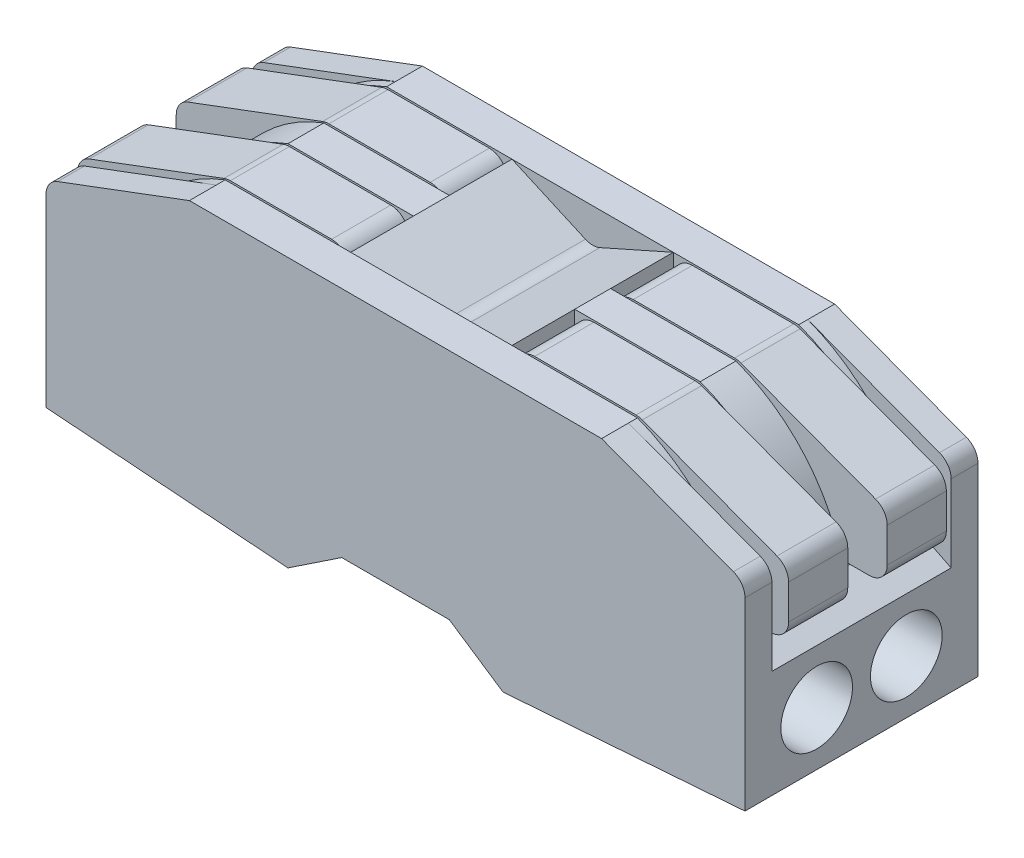
SolidWorks part; units mm, degrees
ref_plane "Alzado" through (0, 0, 0) normal (0, 0, 1) x (1, 0, 0)
ref_plane "Planta" through (0, 0, 0) normal (0, 1, 0) x (1, 0, 0)
ref_plane "Vista lateral" through (0, 0, 0) normal (1, 0, 0) x (0, 0, -1)
sketch "Croquis1" plane through (0, 0, 0) normal (0, 0, 1) x (1, 0, 0)
  line L0 (0, 7.5) -> (0, -7.5) construction
  line L1 (-19.5, 7.5) -> (19.5, 7.5)
  line L2 (-19.5, 7.5) -> (-19.5, -7.5)
  line L3 (-19.5, -7.5) -> (19.5, -7.5)
  line L4 (19.5, 7.5) -> (19.5, -7.5)
  line L5 (-19.5, 7.5) -> (19.5, -7.5) construction
  line L6 (-19.5, -7.5) -> (19.5, 7.5) construction
  point P0 (0, 0)
  dimension "D1" = 39
  dimension "D2" = 15
extrude "Saliente-Extruir1" add sketch "Croquis1" along normal blind 13
sketch "Croquis2" plane through (0, 0, 13) normal (0, 0, 1) x (1, 0, 0)
  line L0 (-19.5, -7.5) -> (19.5, -7.5) construction
  line L1 (0, -7.5) -> (0, 7.5) construction
  line L2 (19.5, 7.5) -> (-19.5, 7.5) construction
  line L3 (-6, -7.5) -> (-19.5, -6.5)
  line L4 (-19.5, 7.5) -> (-19.5, -7.5) construction
  line L5 (-19.5, -6.5) -> (-19.5, -7.5)
  line L6 (-19.5, -7.5) -> (-6, -7.5)
  line L7 (-3, -5.5) -> (-6, -7.5)
  line L8 (-3, -5.5) -> (3, -5.5)
  line L9 (6, -7.5) -> (-6, -7.5)
  line L10 (3, -5.5) -> (6, -7.5)
  line L11 (19.5, -7.5) -> (6, -7.5)
  line L12 (19.5, -6.5) -> (19.5, -7.5)
  line L13 (6, -7.5) -> (19.5, -6.5)
  point P0 (-6, -7.5)
  point P8 (-3, -5.5)
  point P17 (0, -5.5)
  dimension "D1" = 6
  dimension "D2" = 1
  dimension "D3" = 3
  dimension "D4" = 2
extrude "Cortar-Extruir1" cut sketch "Croquis2" against normal blind 13 contours L1 L9 L10 L8 | L1 L8 L7 | L3 | L13 L12 L11 region at (-2.3333, -6.6111, 13) region at (2.3333, -6.6111, 13) region at (-15, -7.1667, 13)
sketch "Croquis3" plane through (0, 0, 13) normal (0, 0, 1) x (1, 0, 0)
  line L0 (19.5, 7.5) -> (-19.5, 7.5) construction
  line L1 (0, 7.5) -> (0, 0) construction
  line L2 (-19.5, 7.5) -> (-19.5, -6.5) construction
  line L3 (-11.5, 7.5) -> (-19.5, 4.5)
  line L4 (-19.5, 4.5) -> (-19.5, 7.5)
  line L5 (-19.5, 7.5) -> (-11.5, 7.5)
  line L6 (19.5, 4.5) -> (19.5, 7.5)
  line L7 (11.5, 7.5) -> (19.5, 4.5)
  line L8 (19.5, 7.5) -> (11.5, 7.5)
  point P0 (-11.5, 7.5)
  point P6 (-19.5, 4.5)
  point P7 (-19.5, -6.5)
  dimension "D1" = 11.5
  dimension "D2" = 11
extrude "Cortar-Extruir2" cut sketch "Croquis3" against normal through all
sketch "Croquis4" plane through (19.5, 0, 0) normal (1, 0, 0) x (0, 0, -1)
  line L0 (0, -6.5) -> (-13, -6.5) construction
  line L2 (-11, -6.5) -> (-11, -7.5)
  line L3 (-11, -7.5) -> (-2, -7.5)
  line L4 (-2, -6.5) -> (-2, -7.5)
  line L5 (-6.5, -6.5) -> (-2, -7.5) construction
  line L6 (-11, -7.5) -> (-6.5, -6.5) construction
  line L7 (0, -7.5) -> (-13, -7.5) construction
  line L8 (0, -6.5) -> (0, 4.5) construction
  line L9 (-2, -6.5) -> (-11, -6.5)
  line L10 (-13, -7.5) -> (-13, -6.5) construction
  point P0 (-6.5, -6.5)
  dimension "D1" = 2
  dimension "D2" = 2
extrude "Cortar-Extruir3" cut sketch "Croquis4" against normal blind 10
sketch "Croquis5" plane through (-19.5, 0, 0) normal (-1, 0, 0) x (0, 0, 1)
  line L0 (0, -6.5) -> (13, -6.5) construction
  line L2 (2, -6.5) -> (2, -7.5)
  line L3 (2, -7.5) -> (11, -7.5)
  line L4 (11, -6.5) -> (11, -7.5)
  line L5 (6.5, -6.5) -> (11, -7.5) construction
  line L6 (2, -7.5) -> (6.5, -6.5) construction
  line L7 (0, -7.5) -> (13, -7.5) construction
  line L8 (13, -7.5) -> (13, -6.5) construction
  line L9 (11, -6.5) -> (2, -6.5)
  point P0 (6.5, -6.5)
  dimension "D1" = 2
extrude "Cortar-Extruir4" cut sketch "Croquis5" against normal blind 10
sketch "Croquis6" plane through (0, 0, 0) normal (0, 0, -1) x (-1, 0, 0)
  line L0 (0, 7.5) -> (0, 1.4685) construction
  line L1 (-11.5, 7.5) -> (11.5, 7.5) construction
  line L2 (4.5, 7.5) -> (-4.5, 7.5)
  line L3 (-4.5, 7.5) -> (0, 5.5)
  line L4 (4.5, 7.5) -> (0, 5.5)
  point P5 (-4.5, 7.5)
  dimension "D1" = 4.5
  dimension "D2" = 2
extrude "Cortar-Extruir5" cut sketch "Croquis6" against normal offset from surface (9 mm away) 2 from offset 2 up to face at (0, -1.5, 13) offset against normal yes
sketch "Croquis7" plane through (-19.5, 0, 0) normal (-1, 0, 0) x (0, 0, 1)
  line L3 (6.5, -6.5) -> (6.5, 4.5) construction
  line L4 (11, -6.5) -> (2, -6.5) construction
  line L5 (0, 4.5) -> (13, 4.5) construction
  line L6 (13, 4.5) -> (13, -6.5) construction
  line L11 (11, -6.5) -> (2, -6.5) construction
  circle A2 centre (9, -3.5) radius 2
  circle A3 centre (4, -3.5) radius 2
  dimension "D1" = 1
  dimension "D3" = 2
extrude "Cortar-Extruir10" cut sketch "Croquis7" against normal blind 15
sketch "Croquis8" plane through (19.5, 0, 0) normal (1, 0, 0) x (0, 0, -1)
  circle A0 centre (-9, -3.5) radius 2
  circle A1 centre (-4, -3.5) radius 2
extrude "Cortar-Extruir11" cut sketch "Croquis8" against normal blind 15
sketch "Croquis9" plane through (0, 7.5, 0) normal (0, 1, 0) x (1, 0, 0)
  line L0 (-19.5, -6.5) -> (19.5, -6.5) construction
  line L1 (-19.5, 0) -> (-19.5, -13) construction
  line L2 (19.5, 0) -> (19.5, -13) construction
  line L3 (4.5, -5.5) -> (19.5, -5.5)
  line L4 (4.5, -11) -> (4.5, -2) construction
  line L5 (-4.5, -5.5) -> (-19.5, -5.5)
  line L6 (-4.5, -11) -> (-4.5, -2) construction
  line L7 (-4.5, -7.5) -> (-19.5, -7.5)
  line L8 (4.5, -7.5) -> (19.5, -7.5)
  line L9 (4.5, -7.5) -> (4.5, -11)
  line L10 (4.5, -11) -> (19.5, -11)
  line L11 (19.5, -11) -> (19.5, -7.5)
  line L12 (4.5, -5.5) -> (4.5, -2)
  line L13 (4.5, -2) -> (19.5, -2)
  line L14 (19.5, -2) -> (19.5, -5.5)
  line L15 (-4.5, -5.5) -> (-4.5, -2)
  line L16 (-4.5, -2) -> (-19.5, -2)
  line L17 (-19.5, -2) -> (-19.5, -5.5)
  line L18 (-19.5, -7.5) -> (-19.5, -11)
  line L19 (-19.5, -11) -> (-4.5, -11)
  line L20 (-4.5, -11) -> (-4.5, -7.5)
  line L21 (-19.5, -13) -> (-11.5, -13) construction
  line L22 (11.5, 0) -> (19.5, 0) construction
  line L23 (11.5, 0) -> (-11.5, 0) construction
  dimension "D1" = 1
  dimension "D2" = 2
  dimension "D3" = 2
  dimension "D4" = 2
extrude "Cortar-Extruir12" cut sketch "Croquis9" against normal blind 7
sketch "Croquis10" plane through (0, 0, 5.5) normal (0, 0, -1) x (-1, 0, 0)
  line L0 (19.5, 0.5) -> (4.5, 0.5) construction
  line L1 (19.5, 4.5) -> (19.5, -6.5) construction
  line L2 (11.5, 7.5) -> (19.5, 4.5) construction
  line L3 (17.5, 0.5) -> (19.5, 0.5)
  line L4 (19.5, 0.5) -> (19.5, 4.5)
  line L5 (19.5, 4.5) -> (11.5, 7.5)
  line L6 (0, 7.5) -> (0, -5.5) construction
  line L7 (4.5, 7.5) -> (-4.5, 7.5) construction
  line L8 (3, -5.5) -> (-3, -5.5) construction
  line L9 (-19.5, 4.5) -> (-11.5, 7.5)
  line L10 (-19.5, 0.5) -> (-19.5, 4.5)
  line L11 (-17.5, 0.5) -> (-19.5, 0.5)
  arc A0 (11.5, 7.5) -> (17.5, 0.5) centre (8.1447, -1.4474) cw
  arc A1 (-11.5, 7.5) -> (-17.5, 0.5) centre (-8.1447, -1.4474) ccw
  point P0 (17.5, 0.5)
  dimension "D1" = 2
extrude "Cortar-Extruir13" cut sketch "Croquis10" against normal blind 6 and the other way blind 4
chamfer "Chaflán1" distance 1 distance2 2 2 edges at (-19.5, 0.5, 6.5) (19.5, 0.5, 6.5) first distance on face at (-19.5, -5.5, 9) first distance on face at (19.5, -1.5, 4)
sketch "Croquis11" plane through (0, 0, 7.5) normal (0, 0, 1) x (1, 0, 0)
  line L0 (11.5, 7.5) -> (19.8336, 4.3749)
  line L1 (4.6639, 0.7529) -> (19.8336, 0.7529)
  line L2 (4.6639, 0.7529) -> (4.6639, 7.5)
  line L3 (4.6639, 7.5) -> (11.5, 7.5)
  line L6 (19.8336, 0.7529) -> (19.8336, 4.3749)
  line L7 (0, 7.5) -> (0, 0) construction
  line L8 (-4.5, 7.5) -> (4.5, 7.5) construction
  line L9 (-19.8336, 0.7529) -> (-19.8336, 4.3749)
  line L10 (-4.6639, 7.5) -> (-11.5, 7.5)
  line L11 (-4.6639, 0.7529) -> (-4.6639, 7.5)
  line L12 (-4.6639, 0.7529) -> (-19.8336, 0.7529)
  line L13 (-11.5, 7.5) -> (-19.8336, 4.3749)
extrude "Saliente-Extruir2" add sketch "Croquis11" along normal offset from surface (3.3 mm away) 0.1 from offset 0.1 separate body up to face at (-9.725, 4.1929, 11)
sketch "Croquis12" plane through (0, 0, 7.6) normal (0, 0, -1) x (-1, 0, 0)
  line L0 (11.5, 7.5) -> (19.8336, 4.3749)
  line L1 (4.6639, 0.7529) -> (19.8336, 0.7529)
  line L2 (4.6639, 0.7529) -> (4.6639, 7.5)
  line L3 (4.6639, 7.5) -> (11.5, 7.5)
  line L4 (19.8336, 0.7529) -> (19.8336, 4.3749)
  line L5 (0, 7.5) -> (0, 0) construction
  line L6 (-19.8336, 0.7529) -> (-19.8336, 4.3749)
  line L7 (-4.6639, 7.5) -> (-11.5, 7.5)
  line L8 (-4.6639, 0.7529) -> (-4.6639, 7.5)
  line L9 (-4.6639, 0.7529) -> (-19.8336, 0.7529)
  line L10 (-11.5, 7.5) -> (-19.8336, 4.3749)
extrude "Saliente-Extruir3" add sketch "Croquis12" along normal offset from surface (3.3 mm away) 0.1 from offset 2.2 separate body up to face at (9.725, 4.1929, 2)
fillet "Redondeo1" radius 1 1 edges at (4.6639, 7.5, 3.75)
fillet "Redondeo2" radius 1 1 edges at (4.6639, 7.5, 9.25)
fillet "Redondeo3" radius 1 1 edges at (-4.6639, 7.5, 3.75)
fillet "Redondeo4" radius 1 1 edges at (-4.6639, 7.5, 9.25)
fillet "Redondeo5" radius 1 1 edges at (-11.5, 7.5, 9.25)
fillet "Redondeo6" radius 1 1 edges at (-11.5, 7.5, 3.75)
fillet "Redondeo7" radius 1 1 edges at (11.5, 7.5, 9.25)
fillet "Redondeo8" radius 1 1 edges at (11.5, 7.5, 3.75)
fillet "Redondeo12" radius 1 1 edges at (0, 5.5, 6.5)
fillet "Redondeo13" radius 1 4 edges at (-19.5, 4.5, 0.75) (-19.5, 4.5, 12.25) (19.5, 4.5, 12.25) (19.5, 4.5, 0.75)
fillet "Redondeo14" radius 1 2 edges at (-19.8336, 0.7529, 3.75) (-19.8336, 4.3749, 3.75)
fillet "Redondeo15" radius 1 2 edges at (-19.8336, 0.7529, 9.25) (-19.8336, 4.3749, 9.25)
fillet "Redondeo16" radius 1 2 edges at (19.8336, 4.3749, 3.75) (19.8336, 0.7529, 3.75)
fillet "Redondeo17" radius 1 2 edges at (19.8336, 0.7529, 9.25) (19.8336, 4.3749, 9.25)
sketch "Croquis13" [suppressed] plane through (0, 0, 0) normal (0, 0, 1) x (1, 0, 0)
  line L1 (-19.5, 7.5) -> (19.5, 7.5)
  line L2 (-19.5, 7.5) -> (-19.5, -7.5)
  line L3 (-19.5, -7.5) -> (19.5, -7.5)
  line L4 (19.5, 7.5) -> (19.5, -7.5)
  line L5 (-19.5, 7.5) -> (19.5, -7.5) construction
  line L6 (-19.5, -7.5) -> (19.5, 7.5) construction
  point P0 (0, 0)
  dimension "D1" = 39
  dimension "D2" = 15
extrude "Saliente-Extruir4" [suppressed] add sketch "Croquis13" along normal blind 18
sketch "Croquis14" [suppressed] plane through (0, 0, 18) normal (0, 0, 1) x (1, 0, 0)
  line L0 (-19.5, -7.5) -> (19.5, -7.5) construction
  line L1 (0, -7.5) -> (0, 7.5) construction
  line L3 (-6, -7.5) -> (-19.5, -6.5)
  line L5 (-19.5, -6.5) -> (-19.5, -7.5)
  line L6 (-19.5, -7.5) -> (-6, -7.5)
  line L7 (-3, -5.5) -> (-6, -7.5)
  line L8 (-3, -5.5) -> (3, -5.5)
  line L9 (6, -7.5) -> (-6, -7.5)
  line L10 (3, -5.5) -> (6, -7.5)
  line L11 (19.5, -7.5) -> (6, -7.5)
  line L12 (19.5, -6.5) -> (19.5, -7.5)
  line L13 (6, -7.5) -> (19.5, -6.5)
  point P0 (-6, -7.5)
  point P2 (0, -7.5)
  point P8 (-3, -5.5)
  point P17 (0, -5.5)
  dimension "D1" = 6
  dimension "D3" = 3
extrude "Cortar-Extruir15" [suppressed] cut sketch "Croquis14" against normal blind 18
sketch "Croquis15" [suppressed] plane through (0, 0, 0) normal (0, 0, 1) x (1, 0, 0)
  line L1 (0, 7.5) -> (0, 0) construction
  line L3 (-11.5, 7.5) -> (-19.5, 4.5)
  line L4 (-19.5, 4.5) -> (-19.5, 7.5)
  line L5 (-19.5, 7.5) -> (-11.5, 7.5)
  line L6 (19.5, 4.5) -> (19.5, 7.5)
  line L7 (11.5, 7.5) -> (19.5, 4.5)
  line L8 (19.5, 7.5) -> (11.5, 7.5)
  point P0 (-11.5, 7.5)
  point P6 (-19.5, 4.5)
  dimension "D1" = 11.5
extrude "Cortar-Extruir17" [suppressed] cut sketch "Croquis15" along normal through all
sketch "Croquis16" [suppressed] plane through (19.5, 0, 0) normal (1, 0, 0) x (0, 0, -1)
  line L0 (0, -6.5) -> (-18, -6.5) construction
  line L2 (-16, -6.5) -> (-16, -7.5)
  line L3 (-16, -7.5) -> (-2, -7.5)
  line L4 (-2, -6.5) -> (-2, -7.5)
  line L5 (-9, -6.5) -> (-2, -7.5) construction
  line L6 (-16, -7.5) -> (-9, -6.5) construction
  line L7 (0, -6.5) -> (0, 4.5) construction
  line L9 (0, -7.5) -> (-18, -7.5) construction
  line L10 (-16, -6.5) -> (-2, -6.5)
  point P0 (-9, -6.5)
  dimension "D1" = 2
  dimension "D2" = 0
extrude "Cortar-Extruir18" [suppressed] cut sketch "Croquis16" against normal blind 10
sketch "Croquis17" [suppressed] plane through (-19.5, 0, 0) normal (-1, 0, 0) x (0, 0, 1)
  line L0 (0, -6.5) -> (18, -6.5) construction
  line L2 (2, -6.5) -> (2, -7.5)
  line L3 (2, -7.5) -> (16, -7.5)
  line L4 (16, -6.5) -> (16, -7.5)
  line L5 (9, -6.5) -> (16, -7.5) construction
  line L6 (2, -7.5) -> (9, -6.5) construction
  line L7 (0, -7.5) -> (18, -7.5) construction
  line L8 (18, 4.5) -> (18, -6.5) construction
  line L9 (2, -6.5) -> (16, -6.5)
  point P0 (9, -6.5)
  dimension "D1" = 2
extrude "Cortar-Extruir19" [suppressed] cut sketch "Croquis17" against normal blind 10
sketch "Croquis18" [suppressed] plane through (0, 0, 18) normal (0, 0, 1) x (1, 0, 0)
  line L0 (0, 7.5) -> (0, 1.4685) construction
  line L2 (4.5, 7.5) -> (-4.5, 7.5)
  line L3 (-4.5, 7.5) -> (0, 5.5)
  line L4 (4.5, 7.5) -> (0, 5.5)
  line L5 (11.5, 7.5) -> (-11.5, 7.5) construction
  point P2 (0, 7.5)
  point P5 (-4.5, 7.5)
  dimension "D1" = 4.5
  dimension "D2" = 2
extrude "Cortar-Extruir20" [suppressed] cut sketch "Croquis18" against normal offset from surface (14 mm away) 2 from offset 2 offset against normal yes
sketch "Croquis19" [suppressed] plane through (0, 7.5, 0) normal (0, 1, 0) x (1, 0, 0)
  line L0 (-19.5, -9) -> (19.5, -9) construction
  line L1 (-19.5, -18) -> (-19.5, 0) construction
  line L2 (19.5, -18) -> (19.5, 0) construction
  line L3 (4.5, -7.5) -> (19.5, -7.5)
  line L4 (4.5, -2) -> (4.5, -16) construction
  line L5 (-4.5, -7.5) -> (-19.5, -7.5)
  line L6 (-4.5, -2) -> (-4.5, -16) construction
  line L7 (-19.5, -7.5) -> (-19.5, -10.5)
  line L8 (-19.5, -10.5) -> (-4.5, -10.5)
  line L9 (-4.5, -7.5) -> (-4.5, -10.5)
  line L10 (4.5, -10.5) -> (19.5, -10.5)
  line L11 (19.5, -10.5) -> (19.5, -7.5)
  line L12 (4.5, -7.5) -> (4.5, -10.5)
  line L13 (-19.5, -9) -> (-19.5, 0) construction
  line L14 (-19.5, -9) -> (-19.5, -18) construction
  line L15 (4.5, -15.375) -> (19.5, -15.375)
  line L16 (-19.5, -13.875) -> (19.5, -13.875) construction
  line L25 (4.5, -15.375) -> (19.5, -15.375)
  line L26 (-19.5, -12.375) -> (-19.5, -15.375)
  line L27 (-4.5, -12.375) -> (-4.5, -15.375)
  line L28 (-4.5, -12.375) -> (-19.5, -12.375)
  line L29 (-19.5, -15.375) -> (-4.5, -15.375)
  line L30 (19.5, -15.375) -> (19.5, -12.375)
  line L31 (4.5, -12.375) -> (4.5, -15.375)
  line L32 (4.5, -12.375) -> (19.5, -12.375)
  line L33 (0, 0) -> (0, -18) construction
  line L34 (11.5, -18) -> (-11.5, -18) construction
  line L35 (-19.5, -12.375) -> (-4.5, -12.375)
  line L36 (-4.5, -15.375) -> (-19.5, -15.375)
  line L37 (4.5, -12.375) -> (19.5, -12.375)
  line L38 (-19.5, -4.125) -> (19.5, -4.125) construction
  line L39 (4.5, -5.625) -> (19.5, -5.625)
  line L40 (-4.5, -2.625) -> (-19.5, -2.625)
  line L41 (-19.5, -5.625) -> (-4.5, -5.625)
  line L42 (4.5, -5.625) -> (19.5, -5.625)
  line L43 (4.5, -5.625) -> (4.5, -2.625)
  line L44 (19.5, -2.625) -> (19.5, -5.625)
  line L45 (-19.5, -2.625) -> (-4.5, -2.625)
  line L46 (-4.5, -5.625) -> (-19.5, -5.625)
  line L47 (-4.5, -5.625) -> (-4.5, -2.625)
  line L48 (-19.5, -5.625) -> (-19.5, -2.625)
  line L49 (4.5, -2.625) -> (19.5, -2.625)
  line L50 (4.5, -2.625) -> (19.5, -2.625)
  dimension "D1" = 3
  dimension "D2" = 1.5
  dimension "D3" = 3
extrude "Cortar-Extruir21" [suppressed] cut sketch "Croquis19" against normal blind 7
sketch "Croquis23" [suppressed] plane through (0, 0, 7.5) normal (0, 0, 1) x (1, 0, 0)
  line L0 (11.5, 7.5) -> (19.8336, 4.3749)
  line L1 (4.6639, 0.7529) -> (19.8336, 0.7529)
  line L2 (4.6639, 0.7529) -> (4.6639, 7.5)
  line L3 (4.6639, 7.5) -> (11.5, 7.5)
  line L4 (19.8336, 0.7529) -> (19.8336, 4.3749)
  line L5 (0, 7.5) -> (0, 0) construction
  line L6 (-19.8336, 0.7529) -> (-19.8336, 4.3749)
  line L7 (-4.6639, 7.5) -> (-11.5, 7.5)
  line L8 (-4.6639, 0.7529) -> (-4.6639, 7.5)
  line L9 (-4.6639, 0.7529) -> (-19.8336, 0.7529)
  line L10 (-11.5, 7.5) -> (-19.8336, 4.3749)
  line L11 (-4.5, 7.5) -> (4.5, 7.5) construction
  point P4 (0, 7.5)
extrude "Saliente-Extruir6" [suppressed] add sketch "Croquis23" along normal offset from surface (2.8 mm away) 0.1 from offset 0.1 separate body
sketch "Croquis25" [suppressed] plane through (0, 0, 12.375) normal (0, 0, 1) x (1, 0, 0)
  line L0 (11.5, 7.5) -> (19.8336, 4.3749)
  line L1 (4.6639, 0.7529) -> (19.8336, 0.7529)
  line L2 (4.6639, 0.7529) -> (4.6639, 7.5)
  line L3 (4.6639, 7.5) -> (11.5, 7.5)
  line L4 (19.8336, 0.7529) -> (19.8336, 4.3749)
  line L5 (0, 7.5) -> (0, 0) construction
  line L6 (-19.8336, 0.7529) -> (-19.8336, 4.3749)
  line L7 (-4.6639, 7.5) -> (-11.5, 7.5)
  line L8 (-4.6639, 0.7529) -> (-4.6639, 7.5)
  line L9 (-4.6639, 0.7529) -> (-19.8336, 0.7529)
  line L10 (-11.5, 7.5) -> (-19.8336, 4.3749)
  line L11 (-4.5, 7.5) -> (4.5, 7.5) construction
  point P16 (0, 7.5)
extrude "Saliente-Extruir7" [suppressed] add sketch "Croquis25" along normal offset from surface (2.8 mm away) 0.1 from offset 0.1 separate body
sketch "Croquis27" [suppressed] plane through (0, 0, 2.625) normal (0, 0, 1) x (1, 0, 0)
  line L0 (11.5, 7.5) -> (19.8336, 4.3749)
  line L1 (4.6639, 0.7529) -> (19.8336, 0.7529)
  line L2 (4.6639, 0.7529) -> (4.6639, 7.5)
  line L3 (4.6639, 7.5) -> (11.5, 7.5)
  line L4 (19.8336, 0.7529) -> (19.8336, 4.3749)
  line L5 (0, 7.5) -> (0, 0) construction
  line L6 (-19.8336, 0.7529) -> (-19.8336, 4.3749)
  line L7 (-4.6639, 7.5) -> (-11.5, 7.5)
  line L8 (-4.6639, 0.7529) -> (-4.6639, 7.5)
  line L9 (-4.6639, 0.7529) -> (-19.8336, 0.7529)
  line L10 (-11.5, 7.5) -> (-19.8336, 4.3749)
  line L12 (-4.5, 7.5) -> (4.5, 7.5) construction
  point P4 (0, 7.5)
  point P16 (0, 7.5)
extrude "Saliente-Extruir8" [suppressed] add sketch "Croquis27" along normal offset from surface (2.8 mm away) 0.1 from offset 0.1 separate body
fillet "Redondeo19" [suppressed] radius 1
fillet "Redondeo20" [suppressed] radius 1
fillet "Redondeo21" [suppressed] radius 1
fillet "Redondeo22" [suppressed] radius 1
fillet "Redondeo24" [suppressed] radius 1
sketch "Croquis26" [suppressed] plane through (-19.5, 0, 0) normal (-1, 0, 0) x (0, 0, 1)
  line L0 (4.125, 0.5) -> (4.125, -6.5) construction
  line L2 (16, -6.5) -> (2, -6.5) construction
  line L3 (9, 0.5) -> (9, -6.5) construction
  line L5 (16, -6.5) -> (2, -6.5) construction
  line L6 (13.875, 0.5) -> (13.875, -6.5) construction
  line L9 (13.875, -3.5) -> (4.125, -3.5) construction
  line L13 (15.375, 0.5) -> (12.375, 0.5) construction
  line L14 (10.5, 0.5) -> (7.5, 0.5) construction
  line L15 (5.625, 0.5) -> (2.625, 0.5) construction
  circle A0 centre (13.875, -3.5) radius 2
  circle A1 centre (9, -3.5) radius 2
  circle A2 centre (4.125, -3.5) radius 2
  dimension "D1" = 4
  dimension "D2" = 1
fillet "Redondeo25" [suppressed] radius 1
fillet "Redondeo26" [suppressed] radius 1
extrude "Cortar-Extruir22" [suppressed] cut sketch "Croquis26" against normal blind 15
sketch "Croquis28" [suppressed] plane through (19.5, 0, 0) normal (1, 0, 0) x (0, 0, -1)
  line L0 (-13.875, 0.5) -> (-13.875, -6.5) construction
  line L1 (-15.375, 0.5) -> (-12.375, 0.5) construction
  line L2 (-2, -6.5) -> (-16, -6.5) construction
  line L3 (-9, 0.5) -> (-9, -6.5) construction
  line L4 (-7.5, 0.5) -> (-10.5, 0.5) construction
  line L5 (-2, -6.5) -> (-16, -6.5) construction
  line L6 (-4.125, 0.5) -> (-4.125, -6.5) construction
  line L7 (-2.625, 0.5) -> (-5.625, 0.5) construction
  circle A0 centre (-4.125, -3.5) radius 2
  circle A1 centre (-9, -3.5) radius 2
  circle A2 centre (-13.875, -3.5) radius 2
  dimension "D1" = 4
  dimension "D2" = 1
extrude "Cortar-Extruir23" [suppressed] cut sketch "Croquis28" against normal blind 15
sketch "Croquis31" [suppressed] plane through (0, 0, 5.625) normal (0, 0, -1) x (-1, 0, 0)
  line L0 (-4.5, 0.5) -> (-19.5, 0.5) construction
  line L1 (-19.5, 0.5) -> (-19.5, 4.5) construction
  line L2 (-11.6698, 7.4363) -> (-19.5, 4.5) construction
  line L3 (-11.5, 7.5) -> (-19.5, 4.5)
  line L4 (-19.5, 4.5) -> (-19.5, 0.5)
  line L5 (-19.5, 0.5) -> (-17.5, 0.5)
  line L6 (0, 7.5) -> (0, 0) construction
  line L7 (-4.5, 7.5) -> (4.5, 7.5) construction
  line L8 (19.5, 0.5) -> (17.5, 0.5)
  line L9 (19.5, 4.5) -> (19.5, 0.5)
  line L10 (11.5, 7.5) -> (19.5, 4.5)
  arc A0 (-11.5, 7.5) -> (-17.5, 0.5) centre (-8.1447, -1.4474) ccw
  arc A1 (11.5, 7.5) -> (17.5, 0.5) centre (8.1447, -1.4474) cw
  dimension "D1" = 2
extrude "Cortar-Extruir24" [suppressed] cut sketch "Croquis31" against normal up to next
sketch "Croquis32" [suppressed] plane through (0, 0, 10.5) normal (0, 0, -1) x (-1, 0, 0)
  line L3 (-11.5, 7.5) -> (-19.5, 4.5)
  line L4 (-19.5, 4.5) -> (-19.5, 0.5)
  line L5 (-19.5, 0.5) -> (-17.5, 0.5)
  line L6 (0, 7.5) -> (0, 0) construction
  line L8 (19.5, 0.5) -> (17.5, 0.5)
  line L9 (19.5, 4.5) -> (19.5, 0.5)
  line L10 (11.5, 7.5) -> (19.5, 4.5)
  line L11 (-4.5, 7.5) -> (4.5, 7.5) construction
  arc A0 (-11.5, 7.5) -> (-17.5, 0.5) centre (-8.1447, -1.4474) ccw
  arc A1 (11.5, 7.5) -> (17.5, 0.5) centre (8.1447, -1.4474) cw
  point P3 (0, 7.5)
extrude "Cortar-Extruir25" [suppressed] cut sketch "Croquis32" against normal up to next
sketch "Croquis33" [suppressed] plane through (0, 0, 15.375) normal (0, 0, -1) x (-1, 0, 0)
  line L0 (-4.5, 7.5) -> (4.5, 7.5) construction
  line L3 (-11.5, 7.5) -> (-19.5, 4.5)
  line L4 (-19.5, 4.5) -> (-19.5, 0.5)
  line L5 (-19.5, 0.5) -> (-17.5, 0.5)
  line L6 (0, 7.5) -> (0, 0) construction
  line L8 (19.5, 0.5) -> (17.5, 0.5)
  line L9 (19.5, 4.5) -> (19.5, 0.5)
  line L10 (11.5, 7.5) -> (19.5, 4.5)
  arc A0 (-11.5, 7.5) -> (-17.5, 0.5) centre (-8.1447, -1.4474) ccw
  arc A1 (11.5, 7.5) -> (17.5, 0.5) centre (8.1447, -1.4474) cw
  point P3 (0, 7.5)
extrude "Cortar-Extruir26" [suppressed] cut sketch "Croquis33" against normal blind 1
sketch "Croquis34" [suppressed] plane through (0, 0, 2.625) normal (0, 0, 1) x (1, 0, 0)
  line L3 (-11.5, 7.5) -> (-19.5, 4.5)
  line L4 (-19.5, 4.5) -> (-19.5, 0.5)
  line L5 (-19.5, 0.5) -> (-17.5, 0.5)
  line L6 (0, 7.5) -> (0, 0) construction
  line L8 (19.5, 0.5) -> (17.5, 0.5)
  line L9 (19.5, 4.5) -> (19.5, 0.5)
  line L10 (11.5, 7.5) -> (19.5, 4.5)
  line L11 (-4.5, 7.5) -> (4.5, 7.5) construction
  arc A0 (-11.5, 7.5) -> (-17.5, 0.5) centre (-8.1447, -1.4474) ccw
  arc A1 (11.5, 7.5) -> (17.5, 0.5) centre (8.1447, -1.4474) cw
  point P3 (0, 7.5)
extrude "Cortar-Extruir27" [suppressed] cut sketch "Croquis34" against normal blind 1
chamfer "Chaflán2" [suppressed] distance 2 distance2 1
